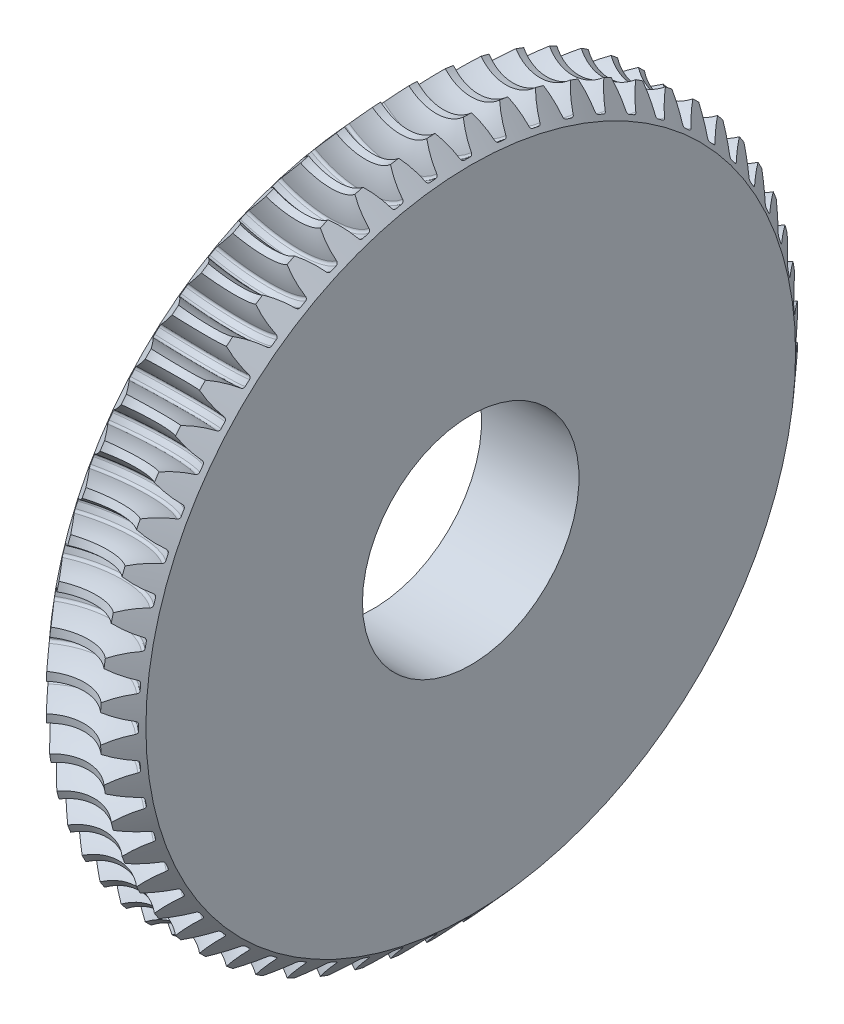
SolidWorks part; units mm, degrees
ref_plane "Front Plane" through (0, 0, 0) normal (0, 0, 1) x (1, 0, 0)
ref_plane "Top Plane" through (0, 0, 0) normal (0, 1, 0) x (1, 0, 0)
ref_plane "Right Plane" through (0, 0, 0) normal (1, 0, 0) x (0, 0, -1)
sketch "Sketch1" plane through (0, 0, 0) normal (0, 0, 1) x (1, 0, 0)
  line L0 (5.0172, 64.4253) -> (9, 60)
  line L1 (-9, 60) -> (9, 60)
  line L2 (-9, 60) -> (-9, 10)
  line L3 (-9, 10) -> (9, 10)
  line L4 (9, 60) -> (9, 10)
  line L5 (-5.0172, 64.4253) -> (-9, 60)
  line L6 (0, 0) -> (61.6263, 0) construction
  arc A0 (6.6896, 62.5671) -> (-6.6896, 62.5671) centre (0, 70) ccw
  arc A2 (-5.0172, 64.4253) -> (5.0172, 64.4253) centre (0, 70) ccw
  circle A3 centre (0, 70) radius 10 construction
  circle A4 centre (0, 70) radius 7.5 construction
  dimension "D6" = 20
  dimension "D1" = 10
  dimension "D2" = 60
  dimension "D3" = 9
  dimension "D4" = 50
  dimension "D5" = 18
  dimension "D7" = 10
  dimension "D9" = 2.5
revolve "Revolve1" add sketch "Sketch1" angle 360 about L6 region at (0, 61.5568, 0) region at (0, 35, 0)
sketch "Sketch5" plane through (0, 0, 0) normal (1, 0, 0) x (0, 0, -1)
  line L0 (0, 70) -> (103.1295, 70) construction
  point P2 (0, 0)
  dimension "D1" = 70
sketch "Sketch7" plane through (0, 0, 0) normal (1, 0, 0) x (0, 0, -1)
  line L0 (0, 0) -> (0, 62) construction
  line L1 (0, 0) -> (1.623, 61.9788) construction
  line L3 (0, 62) -> (0, 70) construction
  line L4 (-4.6157, 65.5314) -> (4.6157, 65.5314)
  arc A2 (0.9591, 57.492) -> (-0.9591, 57.492) centre (0, 0) ccw
  arc A3 (4.6157, 65.5314) -> (0.9591, 57.492) centre (17.8618, 54.6553) ccw
  arc A4 (-4.6157, 65.5314) -> (-0.9591, 57.492) centre (-17.8618, 54.6553) cw
  dimension "D4" = 1.5
revolve "Cut-Revolve1" cut sketch "Sketch7" angle 360 about L0
fillet "Fillet1" radius 0.5 2 edges at (0, 57.492, 0.9591) (0, 57.492, -0.9591)
pattern_circular "CirPattern2" count 60 over 360 about axis through (0, 0, 0) along (-1, 0, 0) of "Fillet1", "Cut-Revolve1" reverse direction yes
sketch "Sketch8" plane through (-9, 0, 0) normal (-1, 0, 0) x (0, 0, 1)
  circle A0 centre (0, 0) radius 20
  dimension "D1" = 40
extrude "Cut-Extrude2" cut sketch "Sketch8" against normal through all
